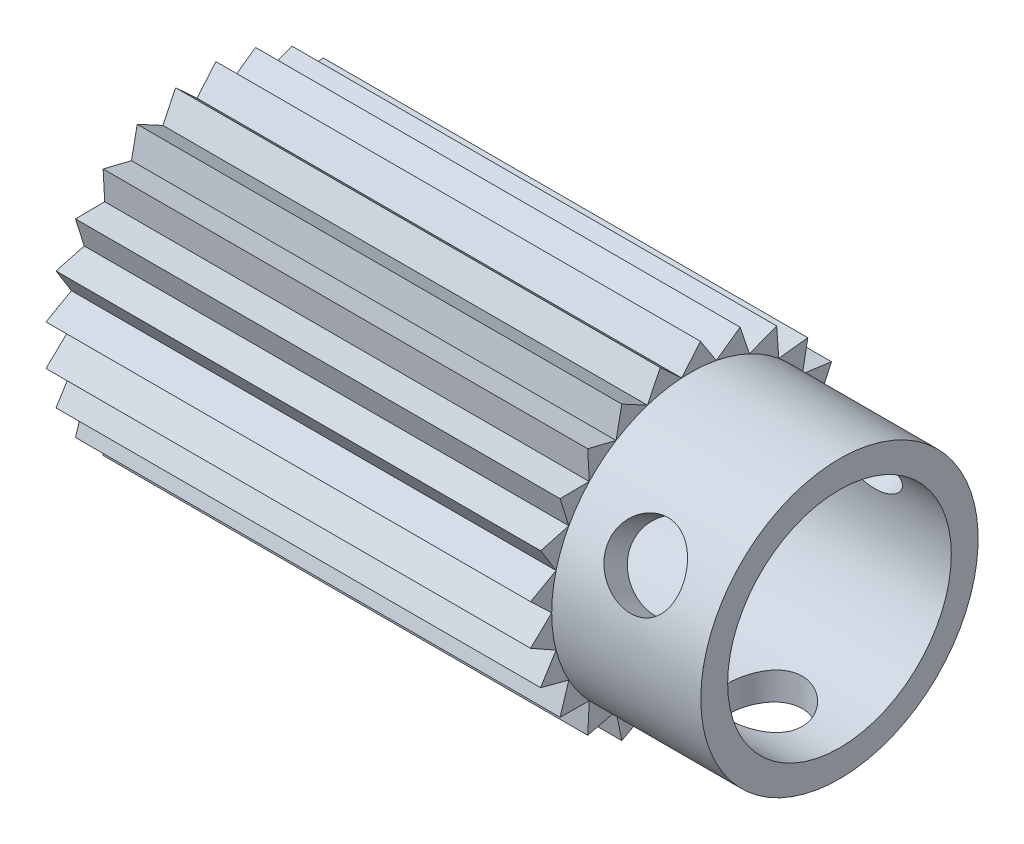
SolidWorks part; units mm, degrees
material "AISI 1020"
ref_plane "X-Y Datum" through (0, 0, 0) normal (0, 0, 1) x (1, 0, 0)
ref_plane "X-Z Datum" through (0, 0, 0) normal (0, 1, 0) x (1, 0, 0)
ref_plane "Y-Z Datum" through (0, 0, 0) normal (1, 0, 0) x (0, 0, -1)
sketch "Sketch1" plane through (0, 0, 0) normal (0, 1, 0) x (1, 0, 0)
  line L0 (-42.0666, 0) -> (42.0666, 0) construction
  line L1 (-30.1625, -15.875) -> (-30.1625, -6.35)
  line L3 (23.8125, -9.525) -> (23.8125, -11.811)
  line L4 (23.8125, -11.811) -> (11.1125, -11.811)
  line L5 (11.1125, -11.811) -> (11.1125, -15.875)
  line L6 (11.1125, -15.875) -> (-30.1625, -15.875)
  line L7 (-30.1625, -6.35) -> (-23.8125, -6.35)
  line L8 (-23.8125, -6.35) -> (-23.8125, -9.525)
  line L9 (-23.8125, -9.525) -> (23.8125, -9.525)
  point P4 (0, -9.525)
  dimension "D1" = 41.275
  dimension "D2" = 6.35
  dimension "D3" = 6.35
  dimension "D4" = 9.525
  dimension "D5" = 11.811
  dimension "D6" = 15.875
  dimension "D7" = 53.975
revolve "Revolve1" add sketch "Sketch1" angle 360 about L0
sketch "Sketch2" plane through (0, 0, 0) normal (0, 1, 0) x (1, 0, 0)
  line L0 (23.8125, -11.811) -> (11.1125, -11.811) construction
  circle A0 centre (17.4625, 0) radius 3.175
  point P7 (17.4625, -11.811)
  dimension "D1" = 6.35
extrude "Cut-Extrude1" cut sketch "Sketch2" against normal through all
pattern_circular "CirPattern1" count 3 over 360 about axis through (-42.0666, 0, 0) along (1, 0, 0) of "Cut-Extrude1" reverse direction yes
sketch "Sketch3" plane through (-30.1625, 0, 0) normal (-1, 0, 0) x (0, 0, 1)
  line L0 (0, 0) -> (15.875, 0) construction
  line L2 (15.7498, 1.9897) -> (0, 0) construction
  line L3 (0, 0) -> (15.3763, 3.948) construction
  line L4 (11.811, 0) -> (13.6078, 1.7191)
  line L5 (13.6078, 1.7191) -> (11.4399, 2.9373)
  line L6 (13.6078, -1.7191) -> (11.811, 0)
  line L7 (11.4399, -2.9373) -> (13.6078, -1.7191)
  line L8 (12.7528, -5.0492) -> (11.4399, -2.9373)
  line L9 (10.3501, -5.69) -> (12.7528, -5.0492)
  line L10 (11.0965, -8.0621) -> (10.3501, -5.69)
  line L11 (8.6098, -8.0852) -> (11.0965, -8.0621)
  line L12 (8.7429, -10.5684) -> (8.6098, -8.0852)
  line L13 (6.3287, -9.9724) -> (8.7429, -10.5684)
  line L14 (5.84, -12.4106) -> (6.3287, -9.9724)
  line L15 (3.6498, -11.2329) -> (5.84, -12.4106)
  line L16 (2.5701, -13.4731) -> (3.6498, -11.2329)
  line L17 (0.7416, -11.7877) -> (2.5701, -13.4731)
  line L18 (-0.8612, -13.6889) -> (0.7416, -11.7877)
  line L19 (-2.2132, -11.6018) -> (-0.8612, -13.6889)
  line L20 (-4.2385, -13.0447) -> (-2.2132, -11.6018)
  line L21 (-5.0289, -10.6869) -> (-4.2385, -13.0447)
  line L22 (-7.3494, -11.5808) -> (-5.0289, -10.6869)
  line L23 (-7.5286, -9.1005) -> (-7.3494, -11.5808)
  line L24 (-9.9985, -9.3892) -> (-7.5286, -9.1005)
  line L25 (-9.5553, -6.9423) -> (-9.9985, -9.3892)
  line L26 (-12.0194, -6.6077) -> (-9.5553, -6.9423)
  line L27 (-10.9816, -4.3479) -> (-12.0194, -6.6077)
  line L28 (-13.2851, -3.411) -> (-10.9816, -4.3479)
  line L29 (-11.7179, -1.4803) -> (-13.2851, -3.411)
  line L30 (-13.716, 0) -> (-11.7179, -1.4803)
  line L31 (-11.7179, 1.4803) -> (-13.716, 0)
  line L32 (-13.2851, 3.411) -> (-11.7179, 1.4803)
  line L33 (-10.9816, 4.3479) -> (-13.2851, 3.411)
  line L34 (-12.0194, 6.6077) -> (-10.9816, 4.3479)
  line L35 (-9.5553, 6.9423) -> (-12.0194, 6.6077)
  line L36 (-9.9985, 9.3892) -> (-9.5553, 6.9423)
  line L37 (-7.5286, 9.1005) -> (-9.9985, 9.3892)
  line L38 (-7.3494, 11.5808) -> (-7.5286, 9.1005)
  line L39 (-5.0289, 10.6869) -> (-7.3494, 11.5808)
  line L40 (-4.2385, 13.0447) -> (-5.0289, 10.6869)
  line L41 (-2.2132, 11.6018) -> (-4.2385, 13.0447)
  line L42 (-0.8612, 13.6889) -> (-2.2132, 11.6018)
  line L43 (0.7416, 11.7877) -> (-0.8612, 13.6889)
  line L44 (2.5701, 13.4731) -> (0.7416, 11.7877)
  line L45 (3.6498, 11.2329) -> (2.5701, 13.4731)
  line L46 (5.84, 12.4106) -> (3.6498, 11.2329)
  line L47 (6.3287, 9.9724) -> (5.84, 12.4106)
  line L48 (8.7429, 10.5684) -> (6.3287, 9.9724)
  line L49 (8.6098, 8.0852) -> (8.7429, 10.5684)
  line L50 (11.0965, 8.0621) -> (8.6098, 8.0852)
  line L51 (10.3501, 5.69) -> (11.0965, 8.0621)
  line L52 (12.7528, 5.0492) -> (10.3501, 5.69)
  line L53 (11.4399, 2.9373) -> (12.7528, 5.0492)
  circle A0 centre (0, 0) radius 15.875 construction
  circle A1 centre (0, 0) radius 11.811 construction
  circle A2 centre (0, 0) radius 13.716 construction
  circle A3 centre (0, 0) radius 11.811 construction
  arc A4 (11.811, 0) -> (11.4399, 2.9373) centre (0, 0) ccw
  arc A5 (11.4399, -2.9373) -> (11.811, 0) centre (0, 0) ccw
  arc A6 (10.3501, -5.69) -> (11.4399, -2.9373) centre (0, 0) ccw
  arc A7 (8.6098, -8.0852) -> (10.3501, -5.69) centre (0, 0) ccw
  arc A8 (6.3287, -9.9724) -> (8.6098, -8.0852) centre (0, 0) ccw
  arc A9 (3.6498, -11.2329) -> (6.3287, -9.9724) centre (0, 0) ccw
  arc A10 (0.7416, -11.7877) -> (3.6498, -11.2329) centre (0, 0) ccw
  arc A11 (-2.2132, -11.6018) -> (0.7416, -11.7877) centre (0, 0) ccw
  arc A12 (-5.0289, -10.6869) -> (-2.2132, -11.6018) centre (0, 0) ccw
  arc A13 (-7.5286, -9.1005) -> (-5.0289, -10.6869) centre (0, 0) ccw
  arc A14 (-9.5553, -6.9423) -> (-7.5286, -9.1005) centre (0, 0) ccw
  arc A15 (-10.9816, -4.3479) -> (-9.5553, -6.9423) centre (0, 0) ccw
  arc A16 (-11.7179, -1.4803) -> (-10.9816, -4.3479) centre (0, 0) ccw
  arc A17 (-11.7179, 1.4803) -> (-11.7179, -1.4803) centre (0, 0) ccw
  arc A18 (-10.9816, 4.3479) -> (-11.7179, 1.4803) centre (0, 0) ccw
  arc A19 (-9.5553, 6.9423) -> (-10.9816, 4.3479) centre (0, 0) ccw
  arc A20 (-7.5286, 9.1005) -> (-9.5553, 6.9423) centre (0, 0) ccw
  arc A21 (-5.0289, 10.6869) -> (-7.5286, 9.1005) centre (0, 0) ccw
  arc A22 (-2.2132, 11.6018) -> (-5.0289, 10.6869) centre (0, 0) ccw
  arc A23 (0.7416, 11.7877) -> (-2.2132, 11.6018) centre (0, 0) ccw
  arc A24 (3.6498, 11.2329) -> (0.7416, 11.7877) centre (0, 0) ccw
  arc A25 (6.3287, 9.9724) -> (3.6498, 11.2329) centre (0, 0) ccw
  arc A26 (8.6098, 8.0852) -> (6.3287, 9.9724) centre (0, 0) ccw
  arc A27 (10.3501, 5.69) -> (8.6098, 8.0852) centre (0, 0) ccw
  arc A28 (11.4399, 2.9373) -> (10.3501, 5.69) centre (0, 0) ccw
  circle A29 centre (0, 0) radius 15.875
  circle M6 centre (0, 0) radius 15.875
  dimension "D3" = 1.905
  dimension "D4" = 25
  dimension "D1" = 7.2
  dimension "D2" = 14.4
extrude "Cut-Extrude2" cut sketch "Sketch3" against normal through all contours L53 L5 L4 L6 L7 L8 L9 L10 L11 L12 L13 L14 L15 L16 L17 L18 L19 L20 L21 L22 L23 L24 L25 L26 L27 L28 L29 L30 L31 L32 L33 L34 L35 L36 L37 L38 L39 L40 L41 L42 L43 L44 L45 L46 L47 L48 L49 L50 L51 M6 region at (-30.1625, 0, -15.426)
